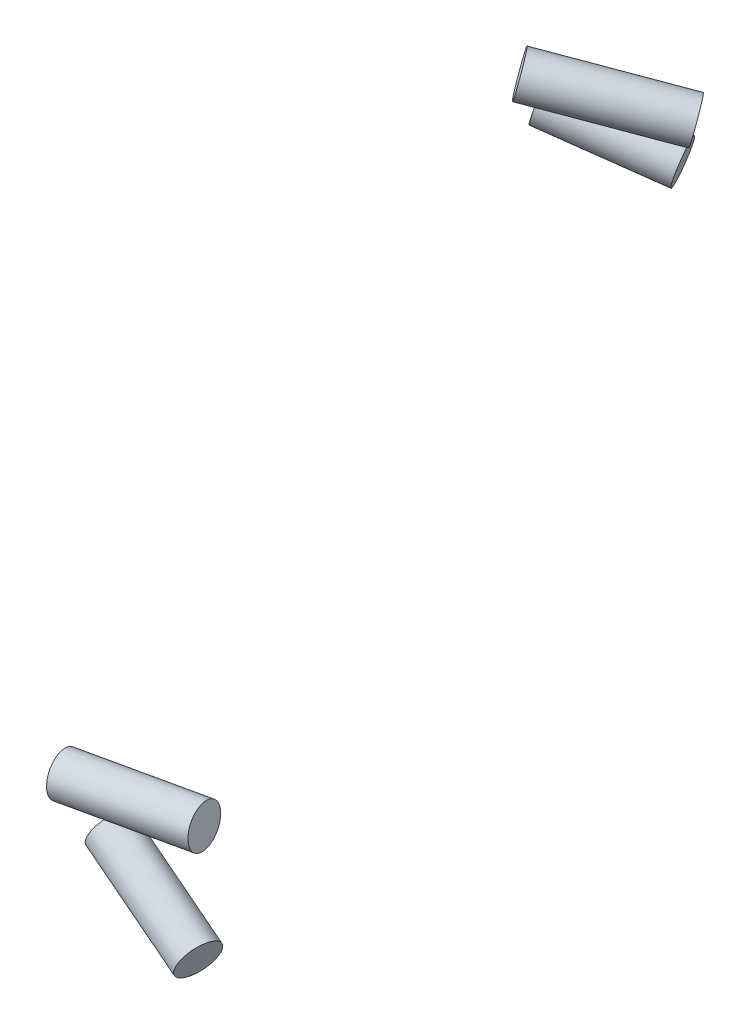
SolidWorks part; units mm, degrees
ref_plane "Plano frontal" through (0, 0, 0) normal (0, 0, 1) x (1, 0, 0)
ref_plane "Plano superior" through (0, 0, 0) normal (0, 1, 0) x (1, 0, 0)
ref_plane "Plano direito" through (0, 0, 0) normal (1, 0, 0) x (0, 0, -1)
sketch3d "SUSP_RL_rocker_bracket_a_eixo"
  line L0 (-231.565, 1104.0299, -80.5983) -> (-268.815, 1120.8704, -87.4288)
sweep "SUSP_RL_rocker_bracket_a" add path "SUSP_RL_rocker_bracket_a_eixo" circular profile diameter 14 parameters "D3"=14
sketch3d "SUSP_RL_rocker_bracket_b_eixo"
  line L0 (-217.9678, 1156.3192, -69.0971) -> (-259.065, 1155.1096, -61.5712)
sweep "SUSP_RL_rocker_bracket_b" add path "SUSP_RL_rocker_bracket_b_eixo" circular profile diameter 14 parameters "D3"=14
sketch3d "SUSP_RL_coilover_bracket_a_eixo"
  line L0 (-243.9847, 1245.821, -259.6731) -> (-276.5823, 1256.3922, -243.5332)
sweep "SUSP_RL_coilover_bracket_a" add path "SUSP_RL_coilover_bracket_a_eixo" circular profile diameter 14 parameters "D3"=14
sketch3d "SUSP_RL_coilover_bracket_b_eixo"
  line L0 (-238.2798, 1261.6845, -258.541) -> (-272.1505, 1271.9554, -231.7798)
sweep "SUSP_RL_coilover_bracket_b" add path "SUSP_RL_coilover_bracket_b_eixo" circular profile diameter 14 parameters "D3"=14
sketch3d "REF_SKETCH"
  line L0 (-259, 1212.7911, -263.659) -> (-251, 1217.5911, -260.059)
  line L1 (-252.6, 1212.1911, -265.059) -> (-257.4, 1218.1911, -258.659)
  line L2 (-255, 1215.1911, -261.859) -> (-210, 1340.3211, -252.929)
  line L3 (-219, 1149.2011, -55.449) -> (-211, 1154.0011, -51.849)
  line L4 (-212.6, 1148.6011, -56.849) -> (-217.4, 1154.6011, -50.449)
  line L5 (-215, 1151.6011, -53.649) -> (-175, 1320.3211, -53.599)
  line L6 (-179, 1317.2, -95.8) -> (-171, 1322, -92.2)
  line L7 (-172.6, 1316.6, -97.2) -> (-177.4, 1322.6, -90.8)
  line L8 (-267.94, 1135.59, -76.3) -> (-259.94, 1140.39, -72.7)
  line L9 (-261.54, 1134.99, -77.7) -> (-266.34, 1140.99, -71.3)
  line L10 (-257.2923, 1161.3349, -56.8698) -> (-270.5877, 1114.6451, -92.1302)
  line L11 (-278.3664, 1261.7738, -239.4565) -> (-270.3664, 1266.5738, -235.8565)
  line L12 (-271.9664, 1261.1738, -240.8565) -> (-276.7664, 1267.1738, -234.4565)
ref_point "P_UCA_IN_FRONT"
ref_axis "A_UCA_PIVOT" through (-255, 1215.1911, -261.859) along (0.3376, 0.9389, 0.067)
ref_point "P_LCA_IN_FRONT"
ref_axis "A_LCA_PIVOT" through (-215, 1151.6011, -53.649) along (0.2307, 0.973, 0.0003)
ref_point "P_TIE_ROD_IN"
ref_point "P_ROCKER_PIVOT"
ref_axis "A_ROCKER" through (-257.2923, 1161.3349, -56.8698) along (-0.2216, -0.7782, -0.5877)
ref_point "P_DAMPER_CHASSIS"
